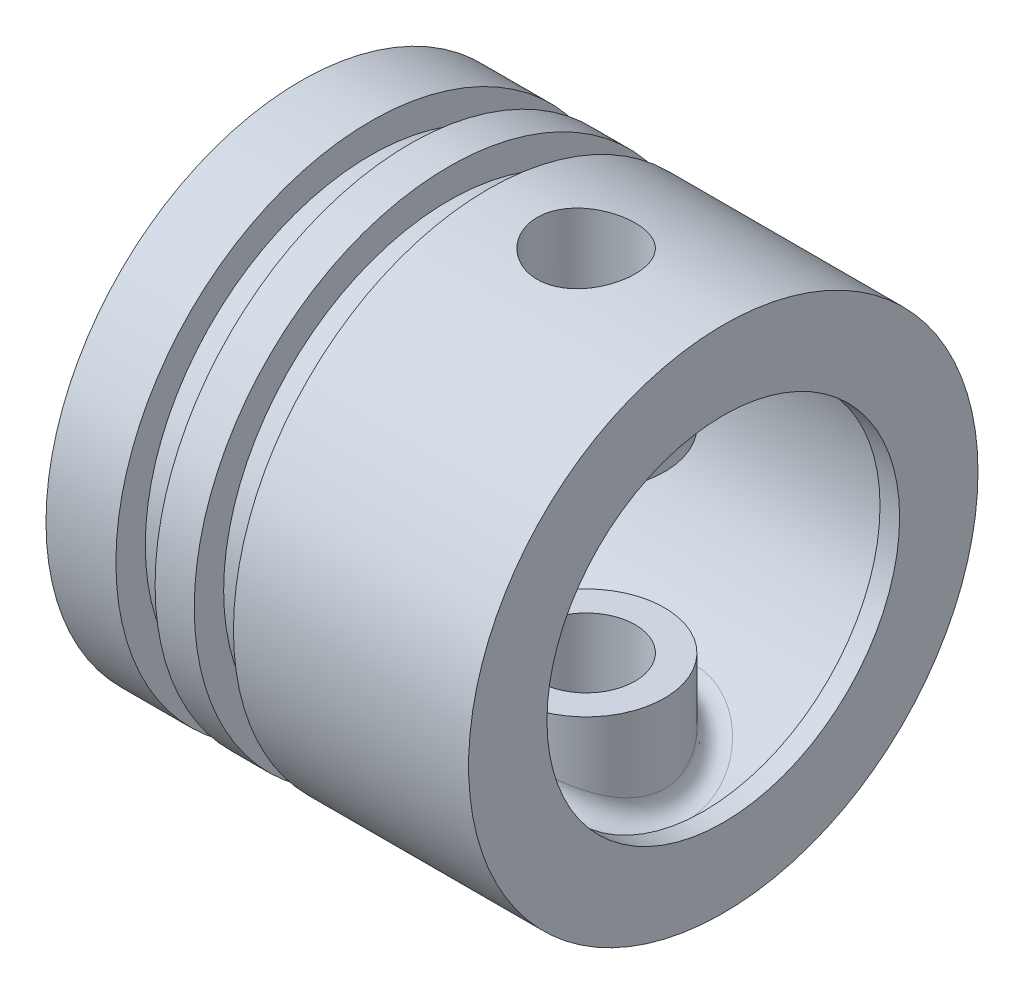
SolidWorks part; units mm, degrees
ref_plane "前视基准面" through (0, 0, 0) normal (0, 0, 1) x (1, 0, 0)
ref_plane "上视基准面" through (0, 0, 0) normal (0, 1, 0) x (1, 0, 0)
ref_plane "右视基准面" through (0, 0, 0) normal (1, 0, 0) x (0, 0, -1)
sketch "草图1" plane through (0, 0, 0) normal (0, 0, 1) x (1, 0, 0)
  line L0 (0, 0) -> (-107.322, 0) construction
  line L1 (28.6, 0) -> (-28.6, 0) construction
  line L2 (0, 18) -> (0, 26)
  line L3 (0, -28.6) -> (0, 28.6) construction
  line L4 (0, 26) -> (-44, 26)
  line L5 (-44, 26) -> (-44, 2)
  line L6 (-44, 2) -> (-38, 2)
  line L7 (-38, 2) -> (-38, 20)
  line L8 (-38, 20) -> (-2, 20)
  line L9 (-2, 20) -> (-2, 18)
  line L10 (-2, 18) -> (0, 18)
  line L11 (0, 18) -> (0, 26)
  line L12 (0, 0) -> (0, 18) construction
  dimension "D1" = 44
  dimension "D2" = 36
  dimension "D3" = 40
  dimension "D4" = 4
  dimension "D5" = 52
  dimension "D6" = 6
  dimension "D7" = 2
revolve "旋转2" add sketch "草图1" angle 360 about L0 region at (-1, 18.5012, 0)
sketch "草图3" plane through (-44, 0, 0) normal (-1, 0, 0) x (0, 0, 1)
  circle A0 centre (0, 0) radius 5
  dimension "D1" = 10
extrude "切除-拉伸1" cut sketch "草图3" against normal blind 4
sketch "草图4" plane through (-40, 0, 0) normal (-1, 0, 0) x (0, 0, 1)
  circle A0 centre (0, 0) radius 4 construction
  circle A1 centre (4, 0) radius 1
  circle A2 centre (0, 4) radius 1
  circle A3 centre (-4, 0) radius 1
  circle A4 centre (0, -4) radius 1
  dimension "D1" = 8
  dimension "D2" = 2
  dimension "D3" = 2
  dimension "D4" = 2
  dimension "D5" = 2
extrude "切除-拉伸2" cut sketch "草图4" against normal blind 4
chamfer "倒角1" distance 2 angle 45 1 edges at (-44, 0, 5)
chamfer "倒角2" distance 1.5 angle 30 1 edges at (-44, 0, -26) first distance on face at (-44, 0, 7)
sketch "草图5" plane through (-44, 0, 0) normal (-1, 0, 0) x (0, 0, 1)
  circle A0 centre (0, 0) radius 23
  dimension "D1" = 46
extrude "切除-拉伸3" cut sketch "草图5" against normal blind 4 from offset 8 flip side to cut offset against normal yes
pattern_linear "阵列(线性)1" count 2 spacing 8 along (1, 0, 0) of "切除-拉伸3"
sketch "草图6" plane through (0, 0, 0) normal (0, 1, 0) x (1, 0, 0)
  line L0 (-24.2, 0) -> (24.2, 0) construction
  line L1 (0, -28.6) -> (0, 28.6) construction
  circle A0 centre (-14, 0) radius 8
  dimension "D1" = 16
  dimension "D2" = 14
extrude "凸台-拉伸1" add sketch "草图6" along normal up to next from offset 10
sketch "草图7" plane through (0, 10, 0) normal (0, -1, 0) x (1, 0, 0)
  circle A0 centre (-14, 0) radius 5
  dimension "D1" = 10
extrude "切除-拉伸4" cut sketch "草图7" against normal through all
fillet "圆角1" radius 2 1 edges at (-15.1772, 18.3681, 7.9129)
mirror "镜向1" about plane through (0, 0, 0) normal (0, 1, 0) of "切除-拉伸4", "凸台-拉伸1", "圆角1"
